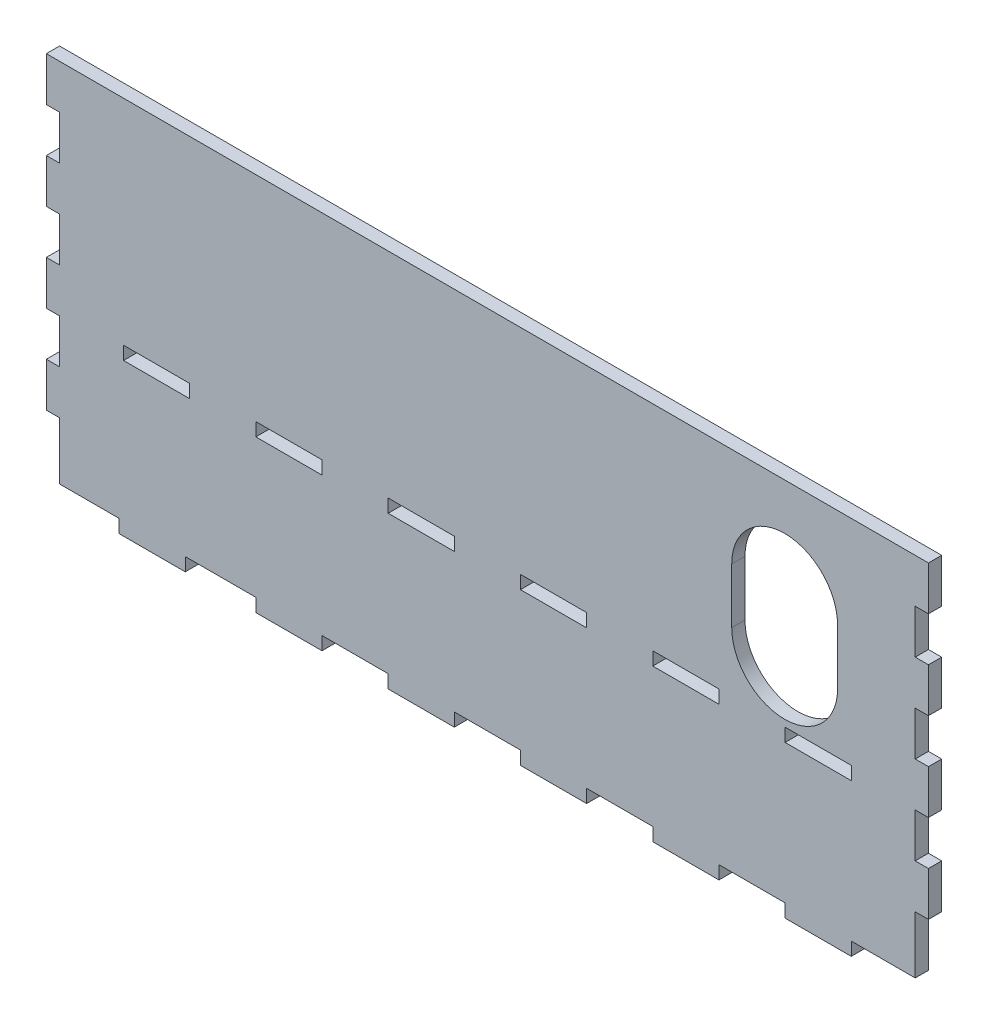
SolidWorks part; units mm, degrees
ref_plane "Front Plane" through (0, 0, 0) normal (0, 0, 1) x (1, 0, 0)
ref_plane "Top Plane" through (0, 0, 0) normal (0, 1, 0) x (1, 0, 0)
ref_plane "Right Plane" through (0, 0, 0) normal (1, 0, 0) x (0, 0, -1)
sketch "Sketch1" plane through (0, 0, 0) normal (0, 0, 1) x (1, 0, 0)
  line L0 (-97, 0) -> (97, 0) construction
  line L1 (0, -25.5) -> (0, 57.5) construction
  line L2 (-97, -12.5) -> (-97, -25.5)
  line L3 (-97, 57.5) -> (97, 57.5)
  line L4 (-100, -12.5) -> (-97, -12.5)
  line L5 (0, -25.5) -> (7.5, -25.5)
  line L6 (-100, -2.5) -> (-100, -12.5)
  line L7 (-97, -2.5) -> (-100, -2.5)
  line L8 (-97, 57.5) -> (-100, 57.5)
  line L9 (-100, 57.5) -> (-100, 47.5)
  line L10 (-100, 47.5) -> (-97, 47.5)
  line L11 (-97, 47.5) -> (-97, 37.5)
  line L12 (-97, 37.5) -> (-100, 37.5)
  line L13 (-100, 37.5) -> (-100, 27.5)
  line L14 (100, 17.5) -> (100, 7.5)
  line L15 (-100, 27.5) -> (-97, 27.5)
  line L16 (-97, 27.5) -> (-97, 17.5)
  line L17 (97, 7.5) -> (100, 7.5)
  line L18 (97, 17.5) -> (100, 17.5)
  line L19 (97, 7.5) -> (97, -2.5)
  line L20 (97, 27.5) -> (97, 17.5)
  line L21 (100, 27.5) -> (97, 27.5)
  line L22 (100, 37.5) -> (100, 27.5)
  line L23 (97, 37.5) -> (100, 37.5)
  line L24 (97, 47.5) -> (97, 37.5)
  line L25 (100, 47.5) -> (97, 47.5)
  line L26 (100, 57.5) -> (100, 47.5)
  line L27 (97, 57.5) -> (100, 57.5)
  line L28 (7.5, -25.5) -> (7.5, -28.5)
  line L29 (7.5, -28.5) -> (22.5, -28.5)
  line L30 (22.5, -28.5) -> (22.5, -25.5)
  line L31 (30, -25.5) -> (37.5, -25.5)
  line L32 (37.5, -25.5) -> (37.5, -28.5)
  line L33 (37.5, -28.5) -> (52.5, -28.5)
  line L34 (52.5, -28.5) -> (52.5, -25.5)
  line L35 (60, -25.5) -> (67.5, -25.5)
  line L36 (67.5, -25.5) -> (67.5, -28.5)
  line L37 (67.5, -28.5) -> (82.5, -28.5)
  line L38 (82.5, -28.5) -> (82.5, -25.5)
  line L39 (22.5, -25.5) -> (30, -25.5)
  line L40 (52.5, -25.5) -> (60, -25.5)
  line L41 (82.5, -25.5) -> (97, -25.5)
  line L42 (0, -25.5) -> (-7.5, -25.5)
  line L43 (-7.5, -25.5) -> (-7.5, -28.5)
  line L44 (-7.5, -28.5) -> (-22.5, -28.5)
  line L45 (-22.5, -28.5) -> (-22.5, -25.5)
  line L46 (-22.5, -25.5) -> (-37.5, -25.5)
  line L47 (-37.5, -25.5) -> (-37.5, -28.5)
  line L48 (-37.5, -28.5) -> (-52.5, -28.5)
  line L49 (-52.5, -28.5) -> (-52.5, -25.5)
  line L50 (-52.5, -25.5) -> (-68.5, -25.5)
  line L51 (-68.5, -25.5) -> (-68.5, -28.5)
  line L52 (97, -2.5) -> (100, -2.5)
  line L53 (100, -2.5) -> (100, -12.5)
  line L54 (100, -12.5) -> (97, -12.5)
  line L55 (97, -12.5) -> (97, -25.5)
  line L56 (-97, 7.5) -> (-97, -2.5)
  line L57 (-97, 17.5) -> (-100, 17.5)
  line L58 (-97, 7.5) -> (-100, 7.5)
  line L59 (-100, 17.5) -> (-100, 7.5)
  line L60 (-68.5, -28.5) -> (-83.5, -28.5)
  line L62 (-83.5, -28.5) -> (-83.5, -25.5)
  line L63 (-83.5, -25.5) -> (-97, -25.5)
  dimension "D2" = 7.5
  dimension "D4" = 83
  dimension "D5" = 10
  dimension "D6" = 194
  dimension "D8" = 7.5
  dimension "D9" = 15
  dimension "D10" = 3
  dimension "D11" = 10
  dimension "D7" = 10
  dimension "D13" = 10
  dimension "D12" = 10
  dimension "D14" = 7.5
  dimension "D15" = 14.5
  dimension "D16" = 10
  dimension "D17" = 10
  dimension "D18" = 3
  dimension "D19" = 15
  dimension "D20" = 15
  dimension "D21" = 15
  dimension "D22" = 16
  dimension "D23" = 15
extrude "Boss-Extrude1" add sketch "Sketch1" along normal blind 3
sketch "Sketch2" plane through (0, 0, 3) normal (0, 0, 1) x (1, 0, 0)
  line L0 (0, -25.5) -> (0, 22.5) construction
  line L1 (-7.5, -25.5) -> (7.5, -25.5) construction
  line L2 (0, 22.5) -> (67.4, 22.5) construction
  line L3 (67.4, 22.5) -> (67.4, 35) construction
  line L4 (55.4, 22.5) -> (55.4, 35)
  line L5 (79.4, 22.5) -> (79.4, 35)
  line L6 (100, 57.5) -> (-100, 57.5) construction
  line L7 (7.5, 6) -> (22.5, 6)
  line L8 (7.5, 6) -> (7.5, 9)
  line L9 (7.5, 9) -> (22.5, 9)
  line L10 (22.5, 6) -> (22.5, 9)
  line L11 (37.5, 6) -> (52.5, 6)
  line L12 (37.5, 6) -> (37.5, 9)
  line L13 (37.5, 9) -> (52.5, 9)
  line L14 (52.5, 6) -> (52.5, 9)
  line L15 (67.5, 6) -> (82.5, 6)
  line L16 (67.5, 6) -> (67.5, 9)
  line L17 (67.5, 9) -> (82.5, 9)
  line L18 (82.5, 6) -> (82.5, 9)
  line L19 (-82.5, 6) -> (-82.5, 9)
  line L20 (-67.5, 9) -> (-82.5, 9)
  line L21 (-67.5, 6) -> (-67.5, 9)
  line L22 (-67.5, 6) -> (-82.5, 6)
  line L23 (-52.5, 6) -> (-52.5, 9)
  line L24 (-37.5, 9) -> (-52.5, 9)
  line L25 (-37.5, 6) -> (-37.5, 9)
  line L26 (-37.5, 6) -> (-52.5, 6)
  line L27 (-22.5, 6) -> (-22.5, 9)
  line L28 (-7.5, 9) -> (-22.5, 9)
  line L29 (-7.5, 6) -> (-7.5, 9)
  line L30 (-7.5, 6) -> (-22.5, 6)
  arc A0 (55.4, 22.5) -> (79.4, 22.5) centre (67.4, 22.5) ccw
  arc A1 (79.4, 35) -> (55.4, 35) centre (67.4, 35) ccw
  point P6 (67.4, 28.75)
  point P46 (0, 9)
  dimension "D4" = 12
  dimension "D1" = 48
  dimension "D2" = 67.4
  dimension "D3" = 12.5
  dimension "D5" = 7.5
  dimension "D6" = 15
  dimension "D7" = 3
  dimension "D8" = 48.5
  dimension "D11" = 3
extrude "Cut-Extrude1" cut sketch "Sketch2" against normal blind 10
